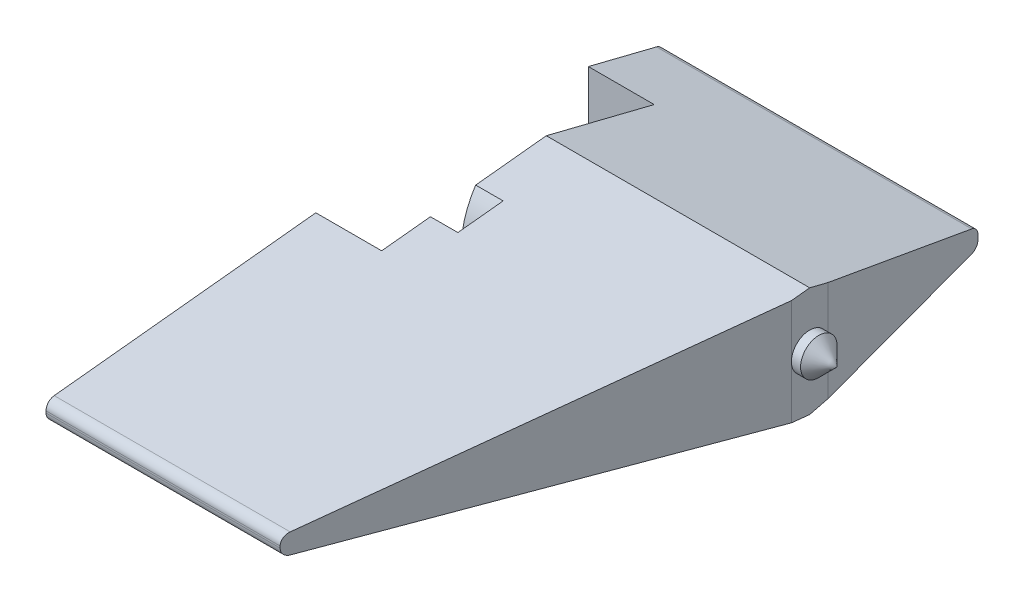
SolidWorks part; units mm, degrees
ref_plane "Front" through (0, 0, 0) normal (0, 0, 1) x (1, 0, 0)
ref_plane "Top" through (0, 0, 0) normal (0, 1, 0) x (1, 0, 0)
ref_plane "Right" through (0, 0, 0) normal (1, 0, 0) x (0, 0, -1)
sketch "Эскиз1" plane through (0, 0, 0) normal (1, 0, 0) x (0, 0, -1)
  line L0 (0, 0) -> (10, 0) construction
  line L1 (0, 0) -> (-23.75, 0) construction
  line L2 (-23.75, -0.5) -> (-23.75, 0.5)
  line L3 (-23.75, 0.5) -> (0, 3)
  line L4 (0, 3) -> (10, 0.5)
  line L5 (10, 0.5) -> (10, -0.5)
  line L6 (0, -3) -> (10, -0.5)
  line L7 (-23.75, -0.5) -> (0, -3)
  circle A0 centre (0, 0) radius 1.95
  dimension "D1" = 3.9
  dimension "D2" = 23.75
  dimension "D3" = 10
  dimension "D4" = 3
  dimension "D5" = 0.5
  dimension "D6" = 0.5
  dimension "D7" = 10
ref_plane "Плоскость1" through (18.5, 0, 0) normal (1, 0, 0) x (0, 0, -1)
sketch "Эскиз2" plane through (18.5, 0, 0) normal (1, 0, 0) x (0, 0, -1)
  line L0 (0, -50.0346) -> (0, 50.2066)
ref_plane "Плоскость2" through (18, 0, 0) normal (1, 0, 0) x (0, 0, -1)
sketch "Эскиз3" plane through (18, 0, 0) normal (1, 0, 0) x (0, 0, -1)
  line L0 (0, 3) -> (10, 0.5) construction
  line L1 (-23.75, 0.5) -> (0, 3) construction
  line L2 (-23.75, -0.5) -> (-23.75, 0.5) construction
  line L3 (-23.75, -0.5) -> (0, -3) construction
  line L4 (0, -3) -> (10, -0.5) construction
  line L5 (10, 0.5) -> (10, -0.5) construction
  line L6 (0, 3) -> (10, 0.5)
  line L7 (-23.75, 0.5) -> (0, 3)
  line L8 (-23.75, -0.5) -> (-23.75, 0.5)
  line L9 (-23.75, -0.5) -> (0, -3)
  line L10 (0, -3) -> (10, -0.5)
  line L11 (10, 0.5) -> (10, -0.5)
  circle A0 centre (0, 0) radius 1
  dimension "D1" = 2
loft "По сечениям1" add section "Эскиз1" section "Эскиз3" connector at (0, -3, 0) connector at (18, -3, 0)
extrude "Вырез-Вытянуть1" cut sketch "Эскиз1<3>" along normal blind 6.5 contours A0 region at (0, 0, 0)
sketch "Эскиз1<3>" plane through (0, 0, 0) normal (1, 0, 0) x (0, 0, -1) same geometry as "Эскиз1"
sketch "Эскиз4" plane through (0, 0, 0) normal (0, 1, 0) x (1, 0, 0)
  line L0 (0, 0) -> (0, 10) construction
  line L1 (0, 5.9) -> (3.6, 5.9)
  line L2 (0, 5.9) -> (0, -9)
  line L3 (0, -9) -> (3.6, -9)
  line L4 (3.6, 5.9) -> (3.6, -9)
  dimension "D1" = 3.6
  dimension "D2" = 5.9
  dimension "D3" = 9
extrude "Вырез-Вытянуть2" cut sketch "Эскиз4" against normal through all both and the other way through all
sketch "Эскиз5" plane through (0, 0, 0) normal (0, 1, 0) x (1, 0, 0)
  line L0 (3.6, -9) -> (3.6, 0) construction
  line L1 (3.6, -6.75) -> (5.1, -6.75)
  line L2 (3.6, -6.75) -> (3.6, -4.65)
  line L3 (3.6, -4.65) -> (5.1, -4.65)
  line L4 (5.1, -6.75) -> (5.1, -4.65)
  dimension "D1" = 1.5
  dimension "D2" = 2.1
  dimension "D3" = 4.65
ref_axis "Ось1" through (6.5, 0, 0) along (-1, 0, 0)
revolve "Вырез-Повернуть1" cut sketch "Эскиз5" angle 40 about axis through (6.5, 0, 0) along (-1, 0, 0) other way angle 40
extrude "Бобышка-Вытянуть1" add sketch "Эскиз3<3>" along normal blind 1.5 contours A0 region at (18, 0, 0)
sketch "Эскиз3<3>" plane through (18, 0, 0) normal (1, 0, 0) x (0, 0, -1) same geometry as "Эскиз3"
chamfer "Фаска1" distance 1 angle 45 1 edges at (19.5, 0, -1)
sketch "Эскиз6" plane through (0, 0, 0) normal (0, 1, 0) x (1, 0, 0)
  line L0 (17.2, 10) -> (18, 1)
  line L1 (18, -50) -> (18, 50) construction
  line L3 (0, 10) -> (18, 10) construction
  line L4 (18, 10) -> (18, 1)
  line L5 (18, -1) -> (12.8, -23.75)
  line L6 (0, -23.75) -> (18, -23.75) construction
  line L7 (12.8, -23.75) -> (18, -23.75)
  line L8 (18, -23.75) -> (18, -1)
  line L9 (12.8, 9.0238) -> (12.8, -23.75)
  line L10 (18, 10) -> (17.2, 10)
  dimension "D1" = 5.2
  dimension "D2" = 1
  dimension "D3" = 1
  dimension "D4" = 0.8
extrude "Вырез-Вытянуть3" cut sketch "Эскиз6" against normal through all both and the other way through all contours L4 | L7 L8 L5 | L10 L0 L4 region at (17.7333, 0, -7) region at (16.2667, 0, 16.1667)
fillet "Скругление1" radius 0.5 4 edges
